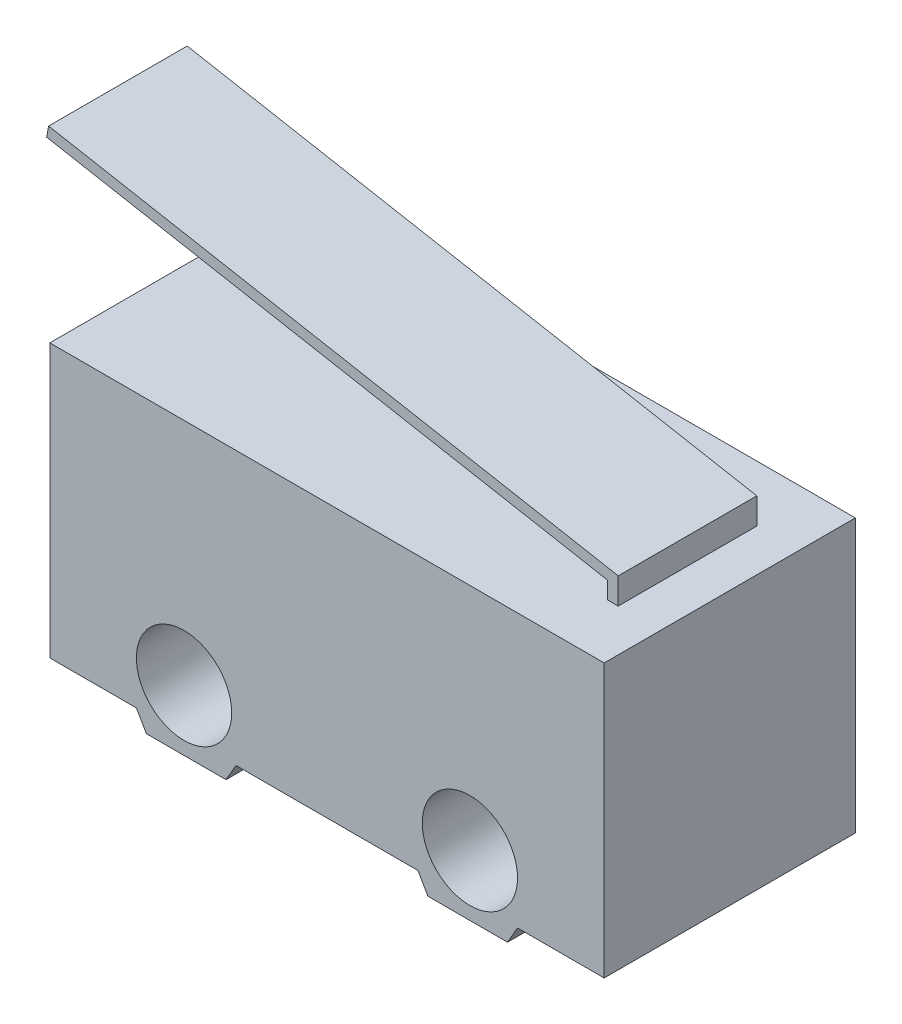
SolidWorks part; units mm, degrees
ref_plane "Front Plane" through (0, 0, 0) normal (0, 0, 1) x (1, 0, 0)
ref_plane "Top Plane" through (0, 0, 0) normal (0, 1, 0) x (1, 0, 0)
ref_plane "Right Plane" through (0, 0, 0) normal (1, 0, 0) x (0, 0, -1)
sketch "Sketch1" plane through (0, 0, 0) normal (0, 0, 1) x (1, 0, 0)
  line L1 (6.4, 3.15) -> (-6.4, 3.15)
  line L2 (6.4, 3.15) -> (6.4, -3.15)
  line L3 (6.4, -3.15) -> (-6.4, -3.15)
  line L4 (-6.4, 3.15) -> (-6.4, -3.15)
  line L5 (6.4, 3.15) -> (-6.4, -3.15) construction
  line L6 (6.4, -3.15) -> (-6.4, 3.15) construction
  point P0 (0, 0)
  dimension "D1" = 12.8
  dimension "D2" = 6.3
extrude "Boss-Extrude1" add sketch "Sketch1" along normal mid plane 5.8
sketch "Sketch2" plane through (0, 0, 2.9) normal (0, 0, 1) x (1, 0, 0)
  line L0 (0, 0) -> (0, -3.15) construction
  line L1 (-6.4, -3.15) -> (6.4, -3.15) construction
  line L2 (0, -3.15) -> (0, 0) construction
  line L3 (6.4, -3.15) -> (6.4, 3.15) construction
  line L4 (6.4, 3.15) -> (-6.4, 3.15) construction
  line L5 (-5.0881, -1.9581) -> (-4.1691, -0.3663)
  line L6 (4.1691, -0.3663) -> (2.3309, -0.3663)
  line L7 (2.3309, -0.3663) -> (1.4119, -1.9581)
  line L8 (1.4119, -1.9581) -> (2.3309, -3.55)
  line L9 (2.3309, -3.55) -> (4.1691, -3.55)
  line L10 (4.1691, -3.55) -> (5.0881, -1.9581)
  line L11 (5.0881, -1.9581) -> (4.1691, -0.3663)
  line L12 (-4.1691, -3.55) -> (-5.0881, -1.9581)
  line L13 (-2.3309, -3.55) -> (-4.1691, -3.55)
  line L14 (-1.4119, -1.9581) -> (-2.3309, -3.55)
  line L15 (-2.3309, -0.3663) -> (-1.4119, -1.9581)
  line L16 (-4.1691, -0.3663) -> (-2.3309, -0.3663)
  circle A0 centre (3.3, -2.15) radius 1.1
  circle A1 centre (-3.3, -2.15) radius 1.1
  circle A2 centre (3.25, -1.9581) radius 1.5919 construction
  circle A3 centre (-3.25, -1.9581) radius 1.5919 construction
  point P8 (2.1, -3.15)
  point P9 (4.0353, -3.15)
  point P16 (4.4, -3.15)
  point P24 (3.3, -1.7453)
  point P33 (-4.4, -3.15)
  point P34 (-2.1, -3.15)
  dimension "D1" = 4.4
  dimension "D2" = 2
  dimension "D3" = 4.2
  dimension "D4" = 4.2
  dimension "D5" = 2
  dimension "D6" = 0.4
extrude "Boss-Extrude3" add sketch "Sketch2" against normal through all contours L6 L7 L8 L9 L10 L11 | L5 L16 L15 L14 L13 L12
extrude "Cut-Extrude2" cut sketch "Sketch2<3>" against normal through all contours A1 | A0
sketch "Sketch2<3>" plane through (0, 0, 2.9) normal (0, 0, 1) x (1, 0, 0) same geometry as "Sketch2"
sketch "Sketch3" plane through (0, 0, 0) normal (0, 0, 1) x (1, 0, 0)
  line L0 (5.3, 3.65) -> (-7.75, 6.05)
  line L1 (6.4, -3.15) -> (6.4, 3.15) construction
  line L2 (-6.4, 3.15) -> (-6.4, -3.15) construction
  line L3 (-6.4, -3.15) -> (-4.4, -3.15) construction
  line L4 (6.4, 3.15) -> (-6.4, 3.15) construction
  line L5 (5.3, 3.65) -> (5.3, 3.15)
  dimension "D1" = 1.1
  dimension "D2" = 1.35
  dimension "D3" = 9.2
  dimension "D4" = 0.5
extrude "Extrude-Thin1" add sketch "Sketch3" along normal mid plane 3.2 thin thin type mid plane wall 0.25
